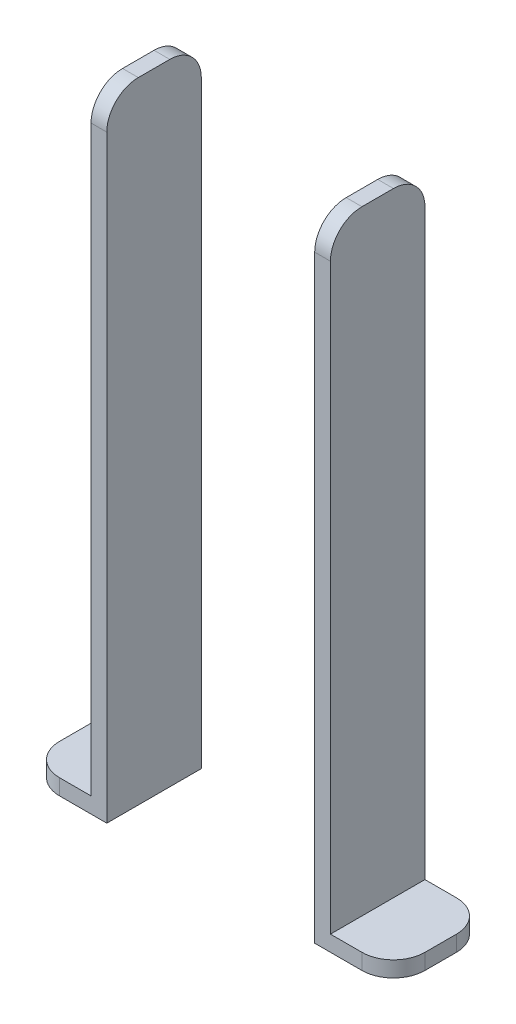
SolidWorks part; units mm, degrees
ref_plane "Front Plane" through (0, 0, 0) normal (0, 0, 1) x (1, 0, 0)
ref_plane "Top Plane" through (0, 0, 0) normal (0, 1, 0) x (1, 0, 0)
ref_plane "Right Plane" through (0, 0, 0) normal (1, 0, 0) x (0, 0, -1)
sketch "Sketch5" plane through (0, 0, 0) normal (0, 0, 1) x (1, 0, 0)
  line L0 (0, 55.0259) -> (0, -52.7661) construction
  line L1 (33, 100) -> (33, -100)
  line L2 (33, -100) -> (58, -100)
  line L3 (58, -100) -> (58, -95)
  line L4 (58, -95) -> (38, -95)
  line L5 (38, -95) -> (38, 100)
  line L6 (38, 100) -> (33, 100)
  line L7 (-38, 100) -> (-33, 100)
  line L8 (-38, -95) -> (-38, 100)
  line L9 (-58, -95) -> (-38, -95)
  line L10 (-58, -100) -> (-58, -95)
  line L11 (-33, -100) -> (-58, -100)
  line L12 (-33, 100) -> (-33, -100)
  point P15 (33, 0)
  dimension "D1" = 33
  dimension "D2" = 25
  dimension "D3" = 5
  dimension "D4" = 5
  dimension "D5" = 200
extrude "Boss-Extrude3" add sketch "Sketch5" along normal blind 15 and the other way blind 15
fillet "Fillet1" radius 10 4 edges at (58, -97.5, -15) (58, -97.5, 15) (35.5, 100, -15) (35.5, 100, 15)
fillet "Fillet2" radius 10 4 edges at (-58, -97.5, -15) (-58, -97.5, 15) (-35.5, 100, -15) (-35.5, 100, 15)
